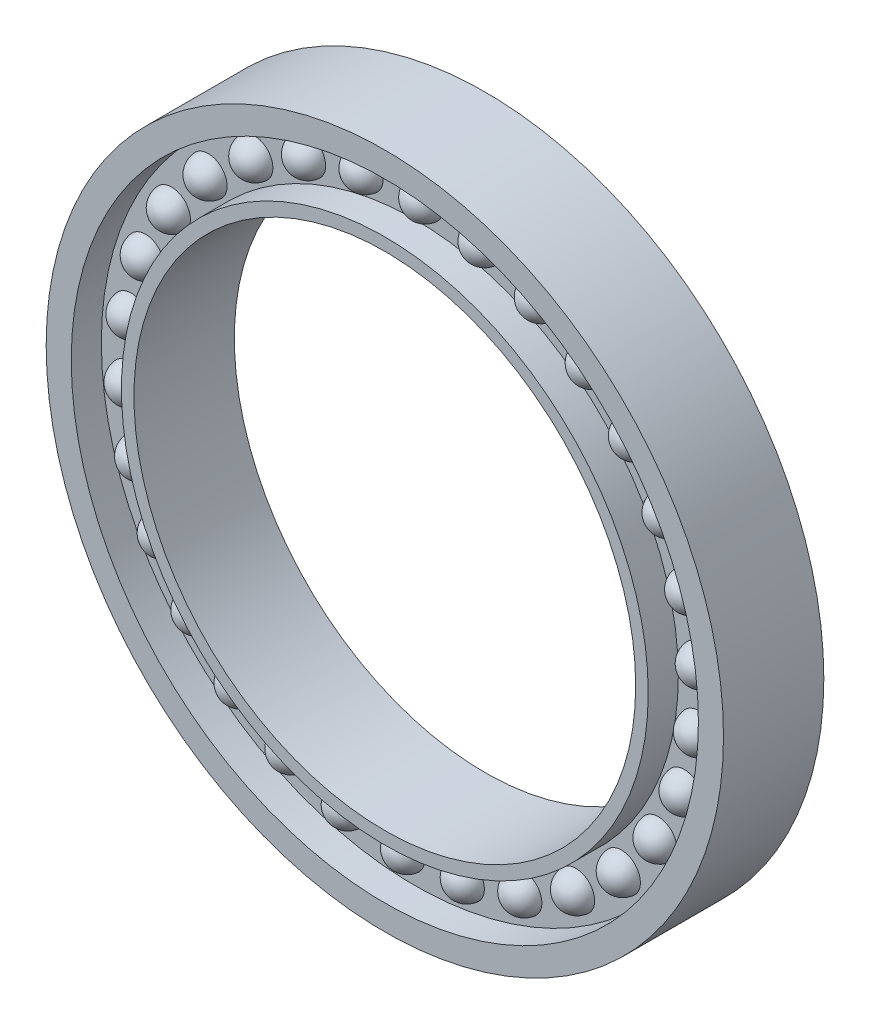
SolidWorks part; units mm, degrees
ref_plane "前视基准面" through (0, 0, 0) normal (0, 0, 1) x (1, 0, 0)
ref_plane "上视基准面" through (0, 0, 0) normal (0, 1, 0) x (1, 0, 0)
ref_plane "右视基准面" through (0, 0, 0) normal (1, 0, 0) x (0, 0, -1)
sketch "草图1" plane through (0, 0, 0) normal (0, 0, 1) x (1, 0, 0)
  circle A0 centre (0, 0) radius 13.5
  circle A1 centre (0, 0) radius 10
  dimension "D1" = 27
  dimension "D2" = 20
extrude "凸台-拉伸1" add sketch "草图1" along normal mid plane 4
sketch "草图2" plane through (0, 0, 2) normal (0, 0, 1) x (1, 0, 0)
  circle A0 centre (0, 0) radius 10.5
  circle A1 centre (0, 0) radius 12.5
  dimension "D1" = 25
  dimension "D2" = 21
extrude "切除-拉伸1" cut sketch "草图2" against normal blind 1.2
mirror "镜向1" about plane through (0, 0, 0) normal (0, 0, 1) of "切除-拉伸1"
sketch "草图4" plane through (0, 0, 0) normal (0, 0, 1) x (1, 0, 0)
  circle A0 centre (0.3622, 11.4093) radius 0.75
  dimension "D1" = 1.5
extrude "凸台-拉伸2" add sketch "草图4" along normal mid plane 3
fillet "圆角1" radius 0.75 1 edges at (1.1122, 11.4093, 1.5)
fillet "圆角2" radius 0.75 1 edges at (1.1122, 11.4093, -1.5)
pattern_circular "阵列(圆周)2" count 30 over 360 about axis through (0, 0, 2) along (0, 0, -1) of "凸台-拉伸2", "圆角1", "圆角2"
